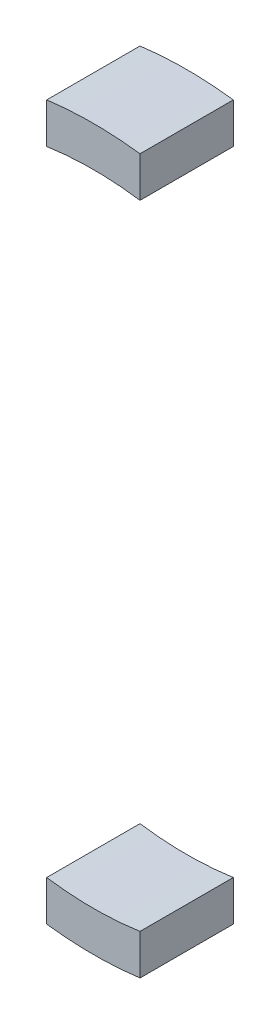
SolidWorks part; units mm, degrees
material "Alliage de zinc AC41A, brut"
ref_plane "Plan de face" through (0, 0, 0) normal (0, 0, 1) x (1, 0, 0)
ref_plane "Plan de dessus" through (0, 0, 0) normal (0, 1, 0) x (1, 0, 0)
ref_plane "Plan de droite" through (0, 0, 0) normal (1, 0, 0) x (0, 0, -1)
sketch "Esquisse1" plane through (0, 0, 0) normal (0, 0, 1) x (1, 0, 0)
  line L0 (0, -13.5) -> (0, 13.5) construction
  line L1 (1.75, 13.3861) -> (1.75, 11.8717)
  line L2 (-1.75, 13.3861) -> (-1.75, 11.8717)
  line L3 (-1.75, -11.8717) -> (-1.75, -13.3861)
  line L4 (1.75, -11.8717) -> (1.75, -13.3861)
  arc A0 (1.75, 13.3861) -> (-1.75, 13.3861) centre (0, 0) ccw
  arc A1 (1.75, 11.8717) -> (-1.75, 11.8717) centre (0, 0) ccw
  arc A2 (-1.75, -13.3861) -> (1.75, -13.3861) centre (0, 0) ccw
  arc A3 (-1.75, -11.8717) -> (1.75, -11.8717) centre (0, 0) ccw
  dimension "D1" = 27
  dimension "D2" = 24
  dimension "D3" = 1.75
  dimension "D4" = 1.75
extrude "Boss.-Extru.1" add sketch "Esquisse1" along normal blind 3.5
